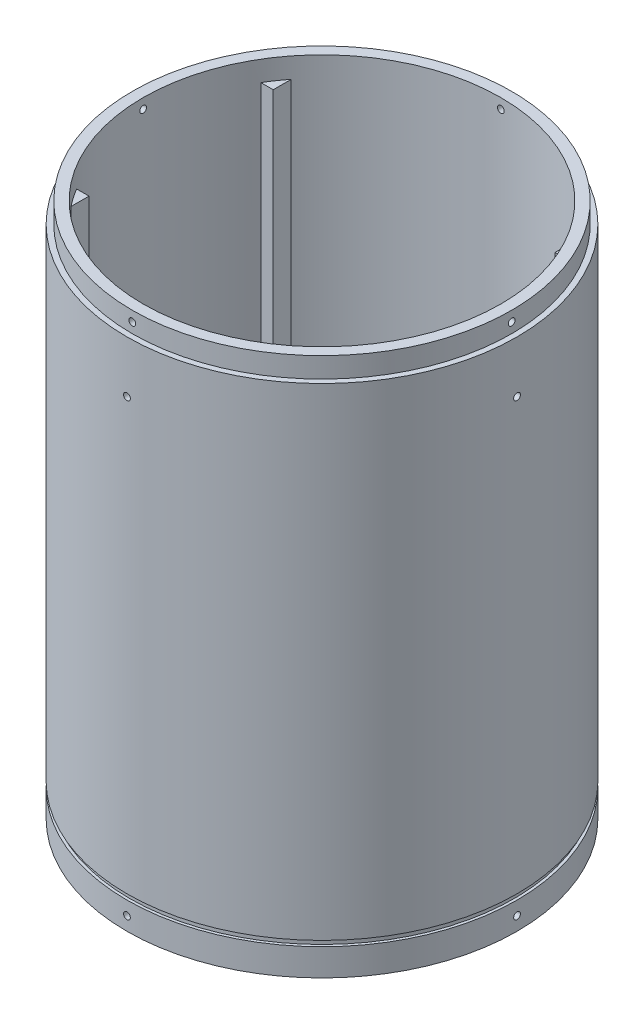
SolidWorks part; units mm, degrees
ref_plane "前基準面" through (0, 0, 0) normal (0, 0, 1) x (1, 0, 0)
ref_plane "上基準面" through (0, 0, 0) normal (0, 1, 0) x (1, 0, 0)
ref_plane "右基準面" through (0, 0, 0) normal (1, 0, 0) x (0, 0, -1)
sketch "草圖6" plane through (0, 0, 0) normal (0, 1, 0) x (1, 0, 0)
  line L0 (0, 0) -> (-95.9878, 0) construction
  line L1 (0, 0) -> (-70, 0) construction
  circle A0 centre (0, 0) radius 66
  circle A1 centre (0, 0) radius 70
  circle A2 centre (0, 0) radius 72
  point P5 (-70, 0)
  point P10 (0, 70)
  point P11 (70, 0)
  point P12 (0, -70)
  dimension "D1" = 2
  dimension "D2" = 4
  dimension "D3" = 144
  dimension "D4" = 4
  dimension "D5" = 70
sketch "草圖7" plane through (0, 0, 0) normal (0, 1, 0) x (1, 0, 0)
  line L1 (-34, 34) -> (34, 34)
  line L2 (-34, 34) -> (-34, -34)
  line L3 (-34, -34) -> (34, -34)
  line L4 (34, 34) -> (34, -34)
  line L5 (-34, 34) -> (34, -34) construction
  line L6 (-34, -34) -> (34, 34) construction
  point P0 (0, 0)
  point P7 (-30, 30)
  point P10 (30, 30)
  point P11 (30, -30)
  point P12 (-30, -30)
  point P13 (0, 0)
  dimension "D1" = 68
  dimension "D2" = 4
  dimension "D3" = 4
extrude "填料-伸長1" add sketch "草圖6" along normal blind 190 contours A2 A1 region at (-71.7964, 0, 0)
extrude "填料-伸長2" add sketch "草圖6<15>" along normal blind 197.5 contours A1 A0 region at (-68.0201, 0, 0)
sketch "草圖6<15>" plane through (0, 0, 0) normal (0, 1, 0) x (1, 0, 0) same geometry as "草圖6"
extrude "填料-伸長3" add sketch "草圖6<16>" along normal blind 3 contours A0 region at (0, 0, 0)
sketch "草圖6<16>" plane through (0, 0, 0) normal (0, 1, 0) x (1, 0, 0) same geometry as "草圖6"
sketch "草圖9" plane through (0, 0, 0) normal (0, 1, 0) x (1, 0, 0)
  line L0 (0, 0) -> (0, 39.247) construction
  line L1 (52, 67.0867) -> (52, -71.5265)
  line L2 (-96.5637, -34) -> (97.4044, -34)
  line L4 (-52, 67.0867) -> (-52, -71.5265)
  line L5 (-56.5685, 34) -> (88.304, 34)
  circle A0 centre (0, 0) radius 66
  circle A1 centre (0, 0) radius 70
  circle A2 centre (0, 0) radius 72
  dimension "D1" = 2
  dimension "D2" = 4
  dimension "D3" = 144
  dimension "D4" = 52
extrude "填料-伸長6" add sketch "草圖9" along normal up to surface (190 mm away) contours L4 A0 L5 | L2 A0 L4 | L1 A0 L2 | L5 A0 L1 region at (53.5564, 0, -36.2624) region at (-53.5564, 0, -36.2624) region at (53.5564, 0, 36.2624) region at (-53.5564, 0, 36.2624) up to face at (0, 190, 70)
sketch "草圖30" plane through (0, 0, 0) normal (1, 0, 0) x (0, 0, -1)
  line L0 (0, 197.5) -> (0, 190) construction
  line L1 (70, 197.5) -> (-70, 197.5) construction
  line L2 (72, 190) -> (-72, 190) construction
  point P6 (0, 193.75)
  dimension "D1" = 3.75
hole_wizard "Ø2.5mm 定位孔3" positions "3D草圖17" profile "草圖31" hole size "Ø2.5" standard "JIS" end condition up to next
sketch3d "3D草圖17"
  point P0 (70, 193.75, 0)
  point P3 (69.9445, 193.4584, -2.7867)
  point P4 (69.9836, 193.6764, -1.5129)
  point P6 (0, 194.1354, 7.5296)
  point P7 (0, 193.642, 0)
  point P10 (69.9999, 193.183, -0.09)
  point P11 (69.9613, 193.6879, -2.3277)
  point P13 (69.9993, 193.6577, -0.3045)
  point P14 (70, 193.7675, 0.0563)
  point P15 (69.9736, 193.7283, 1.9227)
sketch "草圖31" plane through (70, 193.75, 0) normal (0, 1, 0) x (0, 0, -1)
  line L0 (0, 0) -> (0, 70)
  line L1 (0, 70) -> (1.25, 70)
  line L2 (1.25, 70) -> (1.25, 0)
  line L5 (1.25, 0) -> (0, 0)
  line L11 (0, -6.35) -> (0, 107.95) construction
  dimension "貫穿孔直徑" = 2.5
  dimension "貫穿孔深度" = 70
pattern_circular "環狀複製排列1" count 4 over 360 about axis through (0, 197.5, 0) along (0, 1, 0) of "Ø2.5mm 定位孔3"
ref_plane "平面4" through (0, 0, 0) normal (0, 0, 1) x (1, 0, 0)
sketch "草圖33" plane through (0, 0, 0) normal (0, 0, 1) x (1, 0, 0)
  line L5 (-72, 12) -> (-71, 12)
  line L6 (-71, 12) -> (-71, 10)
  line L7 (-71, 10) -> (-72, 10)
  line L9 (72, 0) -> (-72, 0) construction
  line L10 (-72, 12) -> (-72, 10)
  line L11 (-72, 190) -> (-72, 0) construction
  point P16 (0, 0)
  point P17 (-72, 189.3071)
  dimension "D1" = 1
  dimension "D2" = 2
  dimension "D6" = 10
revolve "除料-旋轉1" cut sketch "草圖33" angle 360 about L0
sketch "草圖35" plane through (0, 0, 0) normal (0, 0, 1) x (1, 0, 0)
  line L0 (-72, 10) -> (-72, 0) construction
  point P0 (-72, 5)
hole_wizard "Ø2.5mm 定位孔4" positions "3D草圖20" profile "草圖37" hole size "Ø2.5" standard "JIS"
sketch3d "3D草圖20"
  point P0 (-72, 5, 0)
  point P3 (-69.7213, 3.1686, 17.9704)
  point P4 (-67.2752, 0, 0)
  point P14 (-88.4586, 8.6335, 0)
  point P15 (-72, 0, 0)
  point P16 (-72, 0, 0)
  point P17 (0, 0, 0)
sketch "草圖37" plane through (-72, 5, 0) normal (0, 1, 0) x (0, 0, 1)
  line L0 (0, 0) -> (0, 4.7511)
  line L1 (0, 4.7511) -> (1.25, 4)
  line L2 (1.25, 4) -> (1.25, 0)
  line L5 (1.25, 0) -> (0, 0)
  line L10 (0, 4.7511) -> (-1.25, 4) construction
  line L11 (0, -6.35) -> (0, 107.95) construction
  dimension "鑽孔直徑" = 2.5
  dimension "鑽孔深度" = 4
  dimension "導頭角度" = 118
pattern_circular "環狀複製排列2" count 4 over 360 about axis through (0, 197.5, 0) along (0, -1, 0) of "Ø2.5mm 定位孔4"
hole_wizard "Ø2.5mm 定位孔5" positions "3D草圖21" profile "草圖38" hole size "Ø2.5" standard "JIS"
sketch3d "3D草圖21"
  point P0 (-72, 170.9018, 0)
  point P4 (0, 0, 0)
  point P14 (-71.9903, 21.1527, 1.1836)
  point P16 (-72, 92.0377, 0)
  point P17 (-72, 182.7841, 0)
  point P18 (-72, 178.6099, 0)
  point P19 (-72, 170.9018, 0)
sketch "草圖38" plane through (-72, 170.9018, 0) normal (0, 1, 0) x (0, 0, 1)
  line L0 (0, 0) -> (0, 4.7511)
  line L1 (0, 4.7511) -> (1.25, 4)
  line L2 (1.25, 4) -> (1.25, 0)
  line L5 (1.25, 0) -> (0, 0)
  line L10 (0, 4.7511) -> (-1.25, 4) construction
  line L11 (0, -6.35) -> (0, 107.95) construction
  dimension "鑽孔直徑" = 2.5
  dimension "鑽孔深度" = 4
  dimension "導頭角度" = 118
pattern_circular "環狀複製排列3" count 4 over 360 about axis through (0, 197.5, 0) along (0, -1, 0) of "Ø2.5mm 定位孔5"
sketch "草圖39" plane through (0, 0, 0) normal (0, 1, 0) x (1, 0, 0)
  line L0 (-56.5685, 34) -> (56.5685, 34)
  line L2 (-56.5685, -34) -> (56.5685, -34)
  line L5 (0, 0) -> (0, 19.0172) construction
  line L6 (0, 0) -> (-12.2861, 0) construction
  line L7 (-56.707, 13) -> (-56.707, -13)
  line L8 (-64.707, 13) -> (64.707, 13)
  line L9 (56.707, 13) -> (56.707, -13)
  line L10 (-64.707, -13) -> (64.7924, -12.5675)
  arc A0 (-64.707, -13) -> (-56.5685, -34) centre (0, 0) ccw
  arc A3 (-56.5685, 34) -> (-64.707, 13) centre (0, 0) ccw
  arc A4 (64.707, 13) -> (56.5685, 34) centre (0, 0) ccw
  arc A5 (56.5685, -34) -> (64.7924, -12.5675) centre (0, 0) ccw
  point P4 (0, 0)
  point P5 (0, 0)
  point P8 (0, 0)
  point P9 (0, 0)
  point P12 (-49, 22)
  point P17 (0, 0)
  point P24 (56.707, 0)
  point P25 (0, 0)
  point P27 (-56.707, 0)
  point P28 (0, 0)
  dimension "D1" = 8
  dimension "D2" = 13
  dimension "D5" = 12
sketch "草圖40" plane through (0, 3, 0) normal (0, 1, 0) x (1, 0, 0)
  line L0 (-34, 34) -> (34, 34) construction
  line L1 (-36, 55.3173) -> (36, 55.3173)
  line L2 (-36, 55.3173) -> (-36, 34)
  line L3 (-36, 34) -> (36, 34)
  line L4 (36, 55.3173) -> (36, 34)
  line L5 (-36, 55.3173) -> (36, 34) construction
  line L6 (-36, 34) -> (36, 55.3173) construction
  circle A1 centre (0, 0) radius 66 construction
  point P0 (0, 44.6586)
  point P5 (0, 0)
  point P6 (-6.8906, 47.1616)
  point P7 (-3.201, 47.7926)
  point P8 (-28.1702, 56.1788)
  point P9 (0, 0)
  point P10 (-29.8131, 70)
  point P11 (29.3918, 59)
  point P12 (0, 0)
  point P15 (0, 46.3809)
  point P16 (0, 0)
  point P17 (0, 0)
  point P20 (0, 44.6742)
  point P21 (0, 44.6693)
  point P22 (0, 0)
  dimension "D1" = 21.3173
  dimension "D2" = 72
sketch "草圖41" plane through (0, 3, 0) normal (0, 1, 0) x (1, 0, 0)
  line L0 (0, 0) -> (-95.9878, 0) construction
  line L1 (-63.7154, 5.5) -> (56.2846, 5.5)
  line L2 (-63.7154, 5.5) -> (-63.7154, -5.5)
  line L3 (-63.7154, -5.5) -> (56.2846, -5.5)
  line L4 (56.2846, 5.5) -> (56.2846, -5.5)
  line L5 (-63.7154, 5.5) -> (56.2846, -5.5) construction
  line L6 (-63.7154, -5.5) -> (56.2846, 5.5) construction
  point P0 (-3.7154, 0)
  point P5 (0, 7.1247)
  point P6 (0, 13)
  point P7 (0, 13)
  point P8 (0, 0)
  point P9 (0, 11.5996)
  point P10 (0, 11.9703)
  point P11 (0, 0)
  point P12 (0, 13)
  point P13 (-4.1256, 5.9018)
  point P14 (-1.645, 10.4835)
  point P15 (0, 0)
  point P16 (0, 0)
  point P17 (0, 0)
  point P18 (-8.6756, 0)
  point P21 (0, 0)
  point P22 (-5.6069, 0)
  point P23 (-3.7154, 0)
  dimension "D1" = 11
  dimension "D2" = 120
